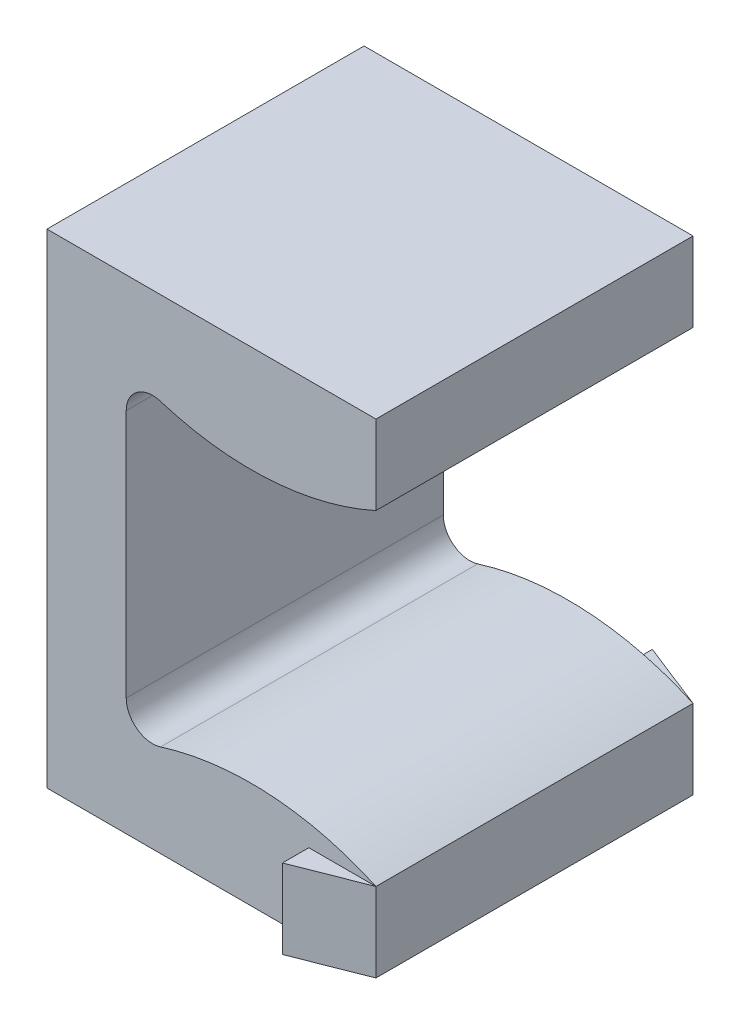
SolidWorks part; units mm, degrees
ref_plane "Front Plane" through (0, 0, 0) normal (0, 0, 1) x (1, 0, 0)
ref_plane "Top Plane" through (0, 0, 0) normal (0, 1, 0) x (1, 0, 0)
ref_plane "Right Plane" through (0, 0, 0) normal (1, 0, 0) x (0, 0, -1)
sketch "Sketch1" plane through (0, 0, 0) normal (0, 0, 1) x (1, 0, 0)
  line L2 (-159.7982, 9.1594) -> (-172.2482, 9.1594)
  line L3 (-172.2482, 9.1594) -> (-172.2482, -9.1594)
  line L7 (-169.2482, -22.8519) -> (-169.2482, 6.1594) construction
  line L13 (-142.8048, 5.1594) -> (-142.8048, -5.1594) construction
  line L23 (-159.7982, 6.1594) -> (-159.7982, 9.1594)
  line L28 (-164.5232, 5.137) -> (-144.5007, 5.137) construction
  line L30 (-169.2482, 6.1594) -> (-169.2482, 5.1594)
  line L34 (-169.2482, 5.1594) -> (-169.2482, -5.1594)
  line L35 (-172.2482, 0) -> (-169.2482, 0) construction
  line L36 (-169.2482, -6.1594) -> (-169.2482, -5.1594)
  line L37 (-159.7982, -6.1594) -> (-159.7982, -9.1594)
  line L38 (-159.7982, -9.1594) -> (-172.2482, -9.1594)
  arc A5 (-169.2482, 6.1594) -> (-159.7982, 6.1594) centre (-164.5232, 16.567) ccw
  arc A6 (-169.2482, -6.1594) -> (-159.7982, -6.1594) centre (-164.5232, -16.567) cw
  point P30 (-142.8048, 0)
  dimension "D6" = 11.43
  dimension "D4" = 3
  dimension "D3" = 3
  dimension "D2" = 1
  dimension "D1" = 18.3188
  dimension "D5" = 12.45
extrude "MainBody" add sketch "Sketch1" along normal mid plane 12
sketch "Sketch3" plane through (0, -9.1594, 0) normal (0, -1, 0) x (1, 0, 0)
  line L0 (-159.7982, -6) -> (-162.3382, -7)
  line L1 (-162.3382, -7) -> (-162.3382, -6)
  line L2 (-172.2482, -6) -> (-159.7982, -6) construction
  line L3 (-162.3382, -6) -> (-159.7982, -6)
  line L5 (55, 0) -> (-55, 0) construction
  line L6 (-162.3382, 6) -> (-159.7982, 6)
  line L7 (-162.3382, 7) -> (-162.3382, 6)
  line L8 (-159.7982, 6) -> (-162.3382, 7)
  dimension "D1" = 2.54
  dimension "D2" = 1
extrude "Hook" add sketch "Sketch3" against normal up to vertex (3 mm away) up to point (-159.7982, -6.1594, -6)
fillet "Fillet2" radius 1 2 edges at (-169.2482, 6.1594, 0) (-169.2482, -6.1594, 0)
sketch "Sketch5" [suppressed] plane through (-172.2482, 0, 0) normal (-1, 0, 0) x (0, 0, 1)
  line L1 (-6, 9.1594) -> (6, 9.1594)
  line L2 (-6, 9.1594) -> (-6, -9.1594)
  line L3 (-6, -9.1594) -> (6, -9.1594)
  line L4 (6, 9.1594) -> (6, -9.1594)
extrude "Boss-Extrude1" [suppressed] add sketch "Sketch5" along normal blind 15
sketch "Sketch6" [suppressed] plane through (0, 9.1594, 0) normal (0, 1, 0) x (1, 0, 0)
  line L0 (-187.2482, -6) -> (-187.2482, 6) construction
  circle A0 centre (-182.2482, 0) radius 3.302
  dimension "D1" = 6.604
  dimension "D2" = 5
extrude "Cut-Extrude2" [suppressed] cut sketch "Sketch6" against normal through all
sketch "Sketch7" [suppressed] plane through (-172.2482, 0, 0) normal (-1, 0, 0) x (0, 0, 1)
  circle A0 centre (0, 0) radius 38.1
  dimension "D1" = 76.2
extrude "Boss-Extrude2" [suppressed] add sketch "Sketch7" along normal blind 5
fillet "Fillet3" [suppressed] radius 1
sketch "Sketch8" [suppressed] plane through (0, 0, 6) normal (0, 0, 1) x (1, 0, 0)
  line L6 (-172.2482, -0.635) -> (-173.4343, -0.635)
  line L8 (-172.2482, 0.635) -> (-173.4343, 0.635)
  line L10 (-172.2482, 0.635) -> (-173.4343, 0.635)
  line L11 (-172.2482, 0.635) -> (-172.2482, -0.635)
  line L12 (-162.3382, -9.1594) -> (-162.3382, -6.1594)
  line L14 (-169.2482, -4.7448) -> (-169.2482, 4.7448)
  line L15 (-159.7982, 6.1594) -> (-159.7982, 9.1594)
  line L16 (-159.7982, 9.1594) -> (-172.2482, 9.1594)
  line L17 (-172.2482, 9.1594) -> (-172.2482, -9.1594)
  line L18 (-172.2482, -9.1594) -> (-162.3382, -9.1594)
  line L21 (-169.2482, -4.7448) -> (-169.2482, 4.7448)
  line L22 (-159.7982, 6.1594) -> (-159.7982, 9.1594)
  line L23 (-159.7982, 9.1594) -> (-172.2482, 9.1594)
  line L24 (-172.2482, 9.1594) -> (-172.2482, -9.1594)
  line L25 (-172.2482, -9.1594) -> (-162.3382, -9.1594)
  line L26 (-172.2482, -0.635) -> (-173.4343, -0.635)
  line L32 (-162.3382, -9.1594) -> (-162.3382, -6.1594)
  line L33 (-162.3382, -6.1594) -> (-159.7982, -6.1594)
  line L34 (-162.3382, -6.1594) -> (-159.7982, -6.1594)
  arc A0 (-173.4343, 0.635) -> (-173.4343, -0.635) centre (-174.5342, 0) ccw
  arc A4 (-159.7982, -6.1594) -> (-167.9665, -5.7043) centre (-164.5232, -17.4347) ccw
  arc A6 (-169.2482, -4.7448) -> (-167.9665, -5.7043) centre (-168.2482, -4.7448) ccw
  arc A7 (-167.9665, 5.7043) -> (-159.7982, 6.1594) centre (-164.5232, 17.4347) ccw
  arc A8 (-159.7982, -6.1594) -> (-167.9665, -5.7043) centre (-164.5232, -17.4347) ccw
  arc A11 (-167.9665, 5.7043) -> (-159.7982, 6.1594) centre (-164.5232, 17.4347) ccw
  arc A12 (-169.2482, -4.7448) -> (-167.9665, -5.7043) centre (-168.2482, -4.7448) ccw
  arc A13 (-167.9665, 5.7043) -> (-169.2482, 4.7448) centre (-168.2482, 4.7448) ccw
  arc A14 (-167.9665, 5.7043) -> (-169.2482, 4.7448) centre (-168.2482, 4.7448) ccw
  point P6 (-172.2482, 0)
  dimension "D2" = 1.27
  dimension "D1" = 0
  dimension "D3" = 2.286
extrude "Slot" [suppressed] add sketch "Sketch8" against normal up to surface (12 mm away) up to face at (-165.7593, -0.5599, -6)
sketch "Sketch10" [suppressed] plane through (0, 0, -6) normal (0, 0, -1) x (-1, 0, 0)
  line L0 (166.0232, -9.1594) -> (172.2482, -9.1594)
  line L3 (172.2482, -9.1594) -> (166.0232, -9.1594)
  line L5 (172.2482, -9.1594) -> (187.9767, -44.4861)
  line L6 (195.4932, -61.3685) -> (192.3182, -61.3685)
  line L7 (159.7982, -6.1594) -> (159.7982, -9.1594)
  line L8 (159.7982, -6.1594) -> (159.7982, -9.1594)
  line L9 (159.7982, -9.1594) -> (172.2482, -9.1594)
  line L10 (172.2482, -9.1594) -> (172.2482, 9.1594)
  line L11 (172.2482, 9.1594) -> (159.7982, 9.1594)
  line L12 (159.7982, 9.1594) -> (159.7982, 6.1594)
  line L13 (169.2482, 6.1594) -> (169.2482, -6.1594)
  line L16 (159.7982, -9.1594) -> (172.2482, -9.1594)
  line L17 (172.2482, -9.1594) -> (172.2482, 9.1594)
  line L18 (172.2482, 9.1594) -> (159.7982, 9.1594)
  line L19 (159.7982, 9.1594) -> (159.7982, 6.1594)
  line L20 (169.2482, 6.1594) -> (169.2482, -6.1594)
  line L21 (195.4932, -61.3685) -> (201.8432, -61.3685)
  line L22 (201.8432, -61.3685) -> (201.8432, -59.781)
  line L24 (192.666, -55.0185) -> (200.9772, -55.0185)
  line L25 (169.0732, -9.1594) -> (192.3182, -61.3685)
  line L28 (201.8432, -59.781) -> (194.7864, -59.781)
  line L31 (193.3728, -56.606) -> (200.9772, -56.606)
  line L42 (200.9772, -55.0185) -> (200.9772, -56.606)
  line L43 (187.9767, -44.4861) -> (195.4932, -61.3685)
  arc A4 (169.2482, -6.1594) -> (159.7982, -6.1594) centre (164.5232, -17.4347) ccw
  arc A5 (159.7982, 6.1594) -> (169.2482, 6.1594) centre (164.5232, 17.4347) ccw
  arc A8 (169.2482, -6.1594) -> (159.7982, -6.1594) centre (164.5232, -17.4347) ccw
  arc A9 (159.7982, 6.1594) -> (169.2482, 6.1594) centre (164.5232, 17.4347) ccw
  dimension "D5" = 6.35
  dimension "D7" = 3.175
  dimension "D8" = 3.175
  dimension "D2" = 57.15
  dimension "D10" = 1.5875
  dimension "D13" = 114
  dimension "D14" = 114
  dimension "D3" = 1.5875
  dimension "D4" = 3.175
extrude "Boss-Extrude3" [suppressed] add sketch "Sketch10" against normal up to surface (12 mm away) up to face at (-165.7593, -0.5599, 6)
sketch "Sketch11" [suppressed] plane through (0, 0, -6) normal (0, 0, -1) x (-1, 0, 0)
  line L0 (159.7982, -9.1594) -> (159.7982, 9.1594)
  line L11 (169.2482, 6.1594) -> (169.2482, -6.1594)
  line L12 (159.7982, -6.1594) -> (159.7982, -9.1594)
  line L13 (159.7982, -9.1594) -> (169.0732, -9.1594)
  line L14 (169.0732, -9.1594) -> (192.3182, -61.3685)
  line L15 (192.3182, -61.3685) -> (201.8432, -61.3685)
  line L16 (201.8432, -61.3685) -> (201.8432, -59.781)
  line L17 (201.8432, -59.781) -> (194.7864, -59.781)
  line L18 (194.7864, -59.781) -> (193.3728, -56.606)
  line L19 (172.2482, -9.1594) -> (172.2482, 9.1594)
  line L20 (172.2482, 9.1594) -> (159.7982, 9.1594)
  line L21 (159.7982, 9.1594) -> (159.7982, 6.1594)
  line L22 (169.2482, 6.1594) -> (169.2482, -6.1594)
  line L23 (159.7982, -6.1594) -> (159.7982, -9.1594)
  line L24 (159.7982, -9.1594) -> (169.0732, -9.1594)
  line L25 (169.0732, -9.1594) -> (192.3182, -61.3685)
  line L26 (192.3182, -61.3685) -> (201.8432, -61.3685)
  line L27 (201.8432, -61.3685) -> (201.8432, -59.781)
  line L28 (201.8432, -59.781) -> (194.7864, -59.781)
  line L29 (194.7864, -59.781) -> (193.3728, -56.606)
  line L30 (172.2482, -9.1594) -> (172.2482, 9.1594)
  line L31 (172.2482, 9.1594) -> (159.7982, 9.1594)
  line L32 (159.7982, 9.1594) -> (159.7982, 6.1594)
  line L37 (193.3728, -56.606) -> (200.9772, -56.606)
  line L38 (193.3728, -56.606) -> (200.9772, -56.606)
  line L39 (200.9772, -56.606) -> (200.9772, -55.0185)
  line L40 (200.9772, -56.606) -> (200.9772, -55.0185)
  line L41 (192.666, -55.0185) -> (172.2482, -9.1594)
  line L42 (192.666, -55.0185) -> (172.2482, -9.1594)
  line L44 (200.9772, -55.0185) -> (192.666, -55.0185)
  line L45 (200.9772, -55.0185) -> (192.666, -55.0185)
  arc A2 (159.7982, 6.1594) -> (169.2482, 6.1594) centre (164.5232, 17.4347) ccw
  arc A3 (169.2482, -6.1594) -> (159.7982, -6.1594) centre (164.5232, -17.4347) ccw
  arc A4 (159.7982, 6.1594) -> (169.2482, 6.1594) centre (164.5232, 17.4347) ccw
  arc A5 (169.2482, -6.1594) -> (159.7982, -6.1594) centre (164.5232, -17.4347) ccw
  dimension "D1" = 0
extrude "Boss-Extrude4" [suppressed] add sketch "Sketch11" against normal up to surface (12 mm away) up to face at (-165.7593, -0.5599, 6)
sketch "Sketch12" [suppressed] plane through (0, 0, -6) normal (0, 0, -1) x (-1, 0, 0)
  line L0 (159.7982, -9.1594) -> (159.7982, -5.9844)
  line L1 (159.7982, -5.9844) -> (162.0842, -5.9844)
  line L3 (162.0842, -5.2351) -> (159.7982, -5.2351)
  line L4 (162.0842, -5.2351) -> (162.0842, -6.7337)
  line L5 (162.0842, -6.7337) -> (159.7982, -6.7337)
  line L6 (159.7982, -5.2351) -> (159.7982, -6.7337)
  line L7 (162.0842, -5.2351) -> (159.7982, -6.7337) construction
  line L8 (162.0842, -6.7337) -> (159.7982, -5.2351) construction
  line L9 (172.2482, 9.1594) -> (159.7982, 9.1594)
  line L10 (159.7982, 9.1594) -> (159.7982, -9.1594)
  line L11 (159.7982, -9.1594) -> (169.0732, -9.1594)
  line L12 (169.0732, -9.1594) -> (192.3182, -61.3685)
  line L13 (192.3182, -61.3685) -> (201.8432, -61.3685)
  line L14 (201.8432, -61.3685) -> (201.8432, -59.781)
  line L15 (201.8432, -59.781) -> (194.7864, -59.781)
  line L16 (194.7864, -59.781) -> (193.3728, -56.606)
  line L17 (172.2482, -9.1594) -> (172.2482, 9.1594)
  line L18 (172.2482, 9.1594) -> (159.7982, 9.1594)
  line L19 (159.7982, 9.1594) -> (159.7982, -9.1594)
  line L20 (159.7982, -9.1594) -> (169.0732, -9.1594)
  line L21 (169.0732, -9.1594) -> (192.3182, -61.3685)
  line L22 (192.3182, -61.3685) -> (201.8432, -61.3685)
  line L23 (201.8432, -61.3685) -> (201.8432, -59.781)
  line L24 (201.8432, -59.781) -> (194.7864, -59.781)
  line L25 (194.7864, -59.781) -> (193.3728, -56.606)
  line L26 (172.2482, -9.1594) -> (172.2482, 9.1594)
  line L38 (193.3728, -56.606) -> (200.9772, -56.606)
  line L39 (193.3728, -56.606) -> (200.9772, -56.606)
  line L40 (200.9772, -56.606) -> (200.9772, -55.0185)
  line L42 (192.666, -55.0185) -> (172.2482, -9.1594)
  line L43 (192.666, -55.0185) -> (172.2482, -9.1594)
  line L45 (200.9772, -56.606) -> (200.9772, -55.0185)
  line L46 (200.9772, -55.0185) -> (192.666, -55.0185)
  line L47 (200.9772, -55.0185) -> (192.666, -55.0185)
  circle A0 centre (162.0842, -5.9844) radius 1.3843
  point P8 (160.9412, -5.9844)
  dimension "D4" = 2.7686
  dimension "D2" = 3.175
  dimension "D3" = 2.286
  dimension "D5" = 1.4986
extrude "Cut-Extrude3" [suppressed] cut sketch "Sketch12" against normal up to surface (12 mm away) up to face at (-165.7593, -0.5599, 6)
pattern_linear "LPattern1" [suppressed] count 4 spacing 4.28 of bodies 117
sketch "Sketch15" [suppressed] plane through (0, 0, 6) normal (0, 0, 1) x (1, 0, 0)
  line L1 (-172.2482, -9.1594) -> (-179.8682, -9.1594)
  line L2 (-172.2482, -9.1594) -> (-172.2482, 47.9906)
  line L3 (-172.2482, 47.9906) -> (-179.8682, 47.9906)
  line L4 (-179.8682, -9.1594) -> (-179.8682, 47.9906)
  dimension "D1" = 7.62
  dimension "D2" = 57.15
extrude "Boss-Extrude6" [suppressed] add sketch "Sketch15" against normal up to surface (12 mm away) up to face at (-165.7593, -0.5599, -6)
sketch "Sketch16" [suppressed] plane through (0, 0, 6) normal (0, 0, 1) x (1, 0, 0)
  line L0 (-172.2482, 9.1594) -> (-172.2482, 47.9906) construction
  line L1 (-172.2482, 44.8156) -> (-174.5342, 44.8156)
  line L2 (-172.2482, 44.8156) -> (-172.2482, 43.2916)
  line L3 (-172.2482, 43.2916) -> (-174.5342, 43.2916)
  line L4 (-174.5342, 44.8156) -> (-174.5342, 43.2916)
  line L5 (-172.2482, 47.9906) -> (-179.8682, 47.9906) construction
  circle A0 centre (-174.5342, 44.0536) radius 1.4605
  dimension "D4" = 2.921
  dimension "D1" = 3.175
  dimension "D2" = 1.524
  dimension "D3" = 2.286
extrude "Cut-Extrude6" [suppressed] cut sketch "Sketch16" against normal up to surface (12 mm away) up to face at (-165.7593, -0.5599, -6)
pattern_linear "LPattern3" [suppressed] count 7 spacing 5.08 of bodies 124
fillet "Fillet5" [suppressed] radius 2.54
equation "\"HookThickness\"= 3mm"
equation "\"D3@Sketch1\"=\"HookThickness\""
equation "\"D4@Sketch1\"=\"HookThickness\""
equation "\"CylinderDiameter\"=3"
equation "\"D1@Sketch7\"=\"CylinderDiameter\""
equation "\"Mount Tolerance\"= .005in"
equation "\"Mount Thickness\"= .0625in"
equation "\"Mount Angle\"= 114"
equation "\"D14@Sketch10\"=\"Mount Angle\""
equation "\"D13@Sketch10\"= \"Mount Angle\""
equation "\"Joint Radius\"= .05in"
equation "\"Joint Thickness\"= .05in"
equation "\"Joint Tolerance\"= .009in"
equation "\"D4@Sketch12\"= (\"Joint Radius\" * 2) + \"Joint Tolerance\""
equation "\"D5@Sketch12\"= \"Joint Thickness\" + \"Joint Tolerance\""
